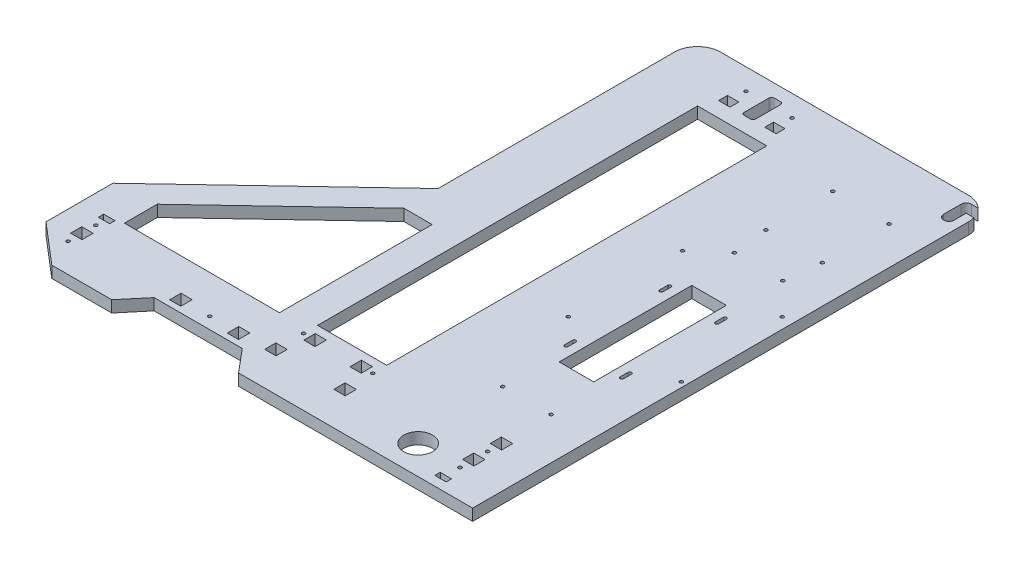
SolidWorks part; units mm, degrees
ref_plane "Front Plane" through (0, 0, 0) normal (0, 0, 1) x (1, 0, 0)
ref_plane "Top Plane" through (0, 0, 0) normal (0, 1, 0) x (1, 0, 0)
ref_plane "Right Plane" through (0, 0, 0) normal (1, 0, 0) x (0, 0, -1)
sketch "Sketch1" plane through (0, 0, 0) normal (0, 1, 0) x (1, 0, 0)
  line L0 (0, 0) -> (-235, 0)
  line L1 (-235, 0) -> (-235, -225)
  line L2 (-235, -225) -> (-380, -362)
  line L3 (-380, -362) -> (-380, -420)
  line L4 (-380, -420) -> (-345, -450)
  line L5 (-345, -450) -> (-293, -450)
  line L6 (-293, -450) -> (-263.6315, -415)
  line L7 (-263.6315, -415) -> (-212.3685, -415)
  line L8 (-212.3685, -415) -> (-183, -450)
  line L9 (-183, -450) -> (0, -450)
  line L10 (0, 0) -> (0, -450)
  line L12 (-293, -450) -> (-183, -450) construction
  dimension "D3" = 235
  dimension "D5" = 58
  dimension "D13" = 190
  dimension "D7" = 35
  dimension "D15" = 52
  dimension "D12" = 30
  dimension "D10" = 35
  dimension "D6" = 380
  dimension "D4" = 450
  dimension "D2" = 50
  dimension "D8" = 50
  dimension "D9" = 110
extrude "Boss-Extrude1" add sketch "Sketch1" along normal blind 10
sketch "Sketch16" plane through (0, 10, 0) normal (0, 1, 0) x (1, 0, 0)
  line L0 (0, -450) -> (20, -450)
  line L1 (20, -450) -> (20, 0)
  line L2 (20, 0) -> (0, 0)
  line L3 (0, 0) -> (0, -450)
  dimension "D1" = 20
  dimension "D2" = 90
extrude "Boss-Extrude2" add sketch "Sketch16" against normal through all
sketch "Sketch2" plane through (0, 10, 0) normal (0, 1, 0) x (1, 0, 0)
  line L0 (-235, -225) -> (-235, -415) construction
  line L1 (-263.6315, -415) -> (-212.3685, -415) construction
  line L2 (-345, -450) -> (-345, -328.931) construction
  line L3 (-235, -225) -> (-380, -362) construction
  line L4 (-345, -358.5097) -> (-235, -254.5787)
  line L5 (-235, -254.5787) -> (-210.5, -254.5787)
  line L6 (-210.5, -254.5787) -> (-210.5, -387)
  line L7 (-210.5, -387) -> (-345, -387)
  line L8 (-345, -387) -> (-345, -358.5097)
  line L9 (0, -450) -> (0, 0) construction
  line L10 (-184.5, -380) -> (-124.5, -380)
  line L11 (-184.5, -380) -> (-184.5, -50.425)
  line L12 (-184.5, -50.425) -> (-124.5, -50.425)
  line L13 (-124.5, -380) -> (-124.5, -50.425)
  line L14 (-124.5, -392.1) -> (-184.5, -392.1) construction
  line L15 (-16, -450) -> (-16, 0) construction
  line L16 (20, 0) -> (-235, 0) construction
  line L17 (-355.9, -440.6571) -> (-355.9, -339.2297) construction
  line L18 (-20.925, -441.85) -> (-11.075, -441.85)
  line L19 (-20.925, -441.85) -> (-20.925, -432.15)
  line L20 (-20.925, -432.15) -> (-11.075, -432.15)
  line L21 (-11.075, -441.85) -> (-11.075, -432.15)
  line L22 (-20.925, -441.85) -> (-11.075, -432.15) construction
  line L23 (-20.925, -432.15) -> (-11.075, -441.85) construction
  line L24 (-20.925, -417.85) -> (-11.075, -417.85)
  line L25 (-20.925, -417.85) -> (-20.925, -408.15)
  line L26 (-20.925, -408.15) -> (-11.075, -408.15)
  line L27 (-11.075, -417.85) -> (-11.075, -408.15)
  line L28 (-20.925, -417.85) -> (-11.075, -408.15) construction
  line L29 (-20.925, -408.15) -> (-11.075, -417.85) construction
  line L30 (-380, -420) -> (-345, -450) construction
  line L32 (-350.975, -408.15) -> (-360.825, -408.15)
  line L33 (-350.975, -408.15) -> (-350.975, -417.85)
  line L34 (-350.975, -417.85) -> (-360.825, -417.85)
  line L35 (-360.825, -408.15) -> (-360.825, -417.85)
  line L36 (-350.975, -408.15) -> (-360.825, -417.85) construction
  line L37 (-350.975, -417.85) -> (-360.825, -408.15) construction
  line L38 (-183, -450) -> (20, -450) construction
  line L39 (-183, -450) -> (20, -450) construction
  line L40 (-173.749, -32.425) -> (-113.749, -32.425) construction
  line L41 (-154.5, -50.425) -> (-154.5, -32.425) construction
  line L42 (-179.425, -27.575) -> (-169.575, -27.575)
  line L43 (-179.425, -27.575) -> (-179.425, -37.275)
  line L44 (-179.425, -37.275) -> (-169.575, -37.275)
  line L45 (-169.575, -27.575) -> (-169.575, -37.275)
  line L46 (-179.425, -27.575) -> (-169.575, -37.275) construction
  line L47 (-179.425, -37.275) -> (-169.575, -27.575) construction
  line L48 (-129.575, -37.275) -> (-139.425, -27.575) construction
  line L49 (-129.575, -27.575) -> (-139.425, -37.275) construction
  line L50 (-139.425, -27.575) -> (-139.425, -37.275)
  line L51 (-129.575, -37.275) -> (-139.425, -37.275)
  line L52 (-129.575, -27.575) -> (-129.575, -37.275)
  line L53 (-129.575, -27.575) -> (-139.425, -27.575)
  line L54 (-174.5, -32.425) -> (-174.5, -18.425) construction
  line L55 (-134.5, -32.425) -> (-134.5, -18.425) construction
  line L56 (-154.5, -380) -> (-154.5, -450) construction
  line L57 (-174.5, -392.1) -> (-134.5, -392.1) construction
  line L58 (-129.65, -397.025) -> (-139.35, -387.175) construction
  line L59 (-179.35, -387.175) -> (-169.65, -387.175)
  line L60 (-179.35, -387.175) -> (-179.35, -397.025)
  line L61 (-179.35, -397.025) -> (-169.65, -397.025)
  line L62 (-169.65, -387.175) -> (-169.65, -397.025)
  line L63 (-179.35, -387.175) -> (-169.65, -397.025) construction
  line L64 (-179.35, -397.025) -> (-169.65, -387.175) construction
  line L65 (-129.65, -387.175) -> (-139.35, -397.025) construction
  line L66 (-139.35, -387.175) -> (-139.35, -397.025)
  line L67 (-129.65, -397.025) -> (-139.35, -397.025)
  line L68 (-129.65, -387.175) -> (-129.65, -397.025)
  line L69 (-129.65, -387.175) -> (-139.35, -387.175)
  line L70 (-119.575, -420.95) -> (-129.425, -411.25) construction
  line L71 (-189.425, -411.25) -> (-179.575, -411.25)
  line L72 (-189.425, -411.25) -> (-189.425, -420.95)
  line L73 (-189.425, -420.95) -> (-179.575, -420.95)
  line L74 (-179.575, -411.25) -> (-179.575, -420.95)
  line L75 (-189.425, -411.25) -> (-179.575, -420.95) construction
  line L76 (-189.425, -420.95) -> (-179.575, -411.25) construction
  line L77 (-119.575, -411.25) -> (-129.425, -420.95) construction
  line L78 (-129.425, -411.25) -> (-129.425, -420.95)
  line L79 (-119.575, -420.95) -> (-129.425, -420.95)
  line L80 (-119.575, -411.25) -> (-119.575, -420.95)
  line L81 (-119.575, -411.25) -> (-129.425, -411.25)
  line L82 (-360.825, -408.15) -> (-11.075, -408.15) construction
  line L83 (-350.975, -393.85) -> (-360.825, -393.85)
  line L84 (-350.975, -393.85) -> (-350.975, -384.15)
  line L85 (-350.975, -384.15) -> (-360.825, -384.15)
  line L86 (-360.825, -393.85) -> (-360.825, -384.15)
  line L87 (-350.975, -393.85) -> (-360.825, -384.15) construction
  line L88 (-350.975, -384.15) -> (-360.825, -393.85) construction
  line L89 (-11.075, -384.15) -> (-20.925, -384.15)
  line L90 (-11.075, -384.15) -> (-11.075, -393.85)
  line L91 (-11.075, -393.85) -> (-20.925, -393.85)
  line L92 (-20.925, -384.15) -> (-20.925, -393.85)
  line L93 (-11.075, -384.15) -> (-20.925, -393.85) construction
  line L94 (-11.075, -393.85) -> (-20.925, -384.15) construction
  circle A0 centre (-16, -425) radius 1.45
  circle A1 centre (-16, -401) radius 1.45
  circle A2 centre (-355.9, -425) radius 1.45
  circle A3 centre (-355.9, -401) radius 1.45
  circle A4 centre (-174.5, -18.425) radius 1.45
  circle A5 centre (-134.5, -18.425) radius 1.45
  circle A6 centre (-124.5, -392.1) radius 1.45
  circle A7 centre (-184.5, -392.1) radius 1.45
  point P25 (-16, -437)
  point P30 (-16, -413)
  point P44 (-355.9, -413)
  point P58 (-355.9, -389)
  point P61 (-174.5, -32.425)
  point P72 (-134.5, -32.425)
  point P85 (-174.5, -392.1)
  point P94 (-134.5, -392.1)
  point P95 (-184.5, -416.1)
  point P104 (-124.5, -416.1)
  point P105 (-154.5, -392.1)
  point P111 (-16, -389)
  dimension "D13" = 2.9
  dimension "D14" = 2.9
  dimension "D23" = 2.9
  dimension "D24" = 2.9
  dimension "D31" = 2.9
  dimension "D37" = 2.9
  dimension "D1" = 21.5
  dimension "D2" = 28
  dimension "D3" = 24.5
  dimension "D4" = 60
  dimension "D7" = 26
  dimension "D8" = 9.7
  dimension "D9" = 9.85
  dimension "D10" = 9.85
  dimension "D11" = 9.7
  dimension "D12" = 24
  dimension "D15" = 24
  dimension "D19" = 9.85
  dimension "D20" = 9.7
  dimension "D26" = 12
  dimension "D27" = 9.85
  dimension "D28" = 9.7
  dimension "D33" = 9.7
  dimension "D38" = 9.85
  dimension "D39" = 9.7
  dimension "D41" = 24
  dimension "D34" = 30
  dimension "D36" = 12.1
  dimension "D30" = 18
  dimension "D29" = 40
  dimension "D17" = 13
  dimension "D32" = 14
  dimension "D35" = 20
  dimension "D16" = 12
  dimension "D21" = 90
  dimension "D25" = 24
  dimension "D5" = 359.75
  dimension "D22" = 349.75
  dimension "D40" = 30
  dimension "D6" = 70
  dimension "D42" = 0
  dimension "D43" = 0
  dimension "D18" = 16
  dimension "D44" = 9.85
  dimension "D45" = 24
  dimension "D46" = 24
extrude "Cut-Extrude1" cut sketch "Sketch2" against normal through all
fillet "Fillet1" radius 20 2 edges at (-235, 5, 0) (20, 5, 0)
sketch "Sketch11" plane through (0, 10, 0) normal (0, 1, 0) x (1, 0, 0)
  line L0 (-124.5, -215.2125) -> (20, -215.2125) construction
  line L1 (20, -450) -> (20, -20) construction
  line L3 (-52.25, -215.2125) -> (-52.25, -450) construction
  line L6 (-124.5, -380) -> (-124.5, -50.425) construction
  line L8 (-183, -450) -> (20, -450) construction
  circle A0 centre (-52.25, -425) radius 12.5
  circle A1 centre (-16, -425) radius 1.45 construction
  dimension "D1" = 25
  dimension "D2" = 0
  dimension "D3" = 0
extrude "WiringHole" cut sketch "Sketch11" against normal through all
sketch "Sketch9" [suppressed] plane through (0, 10, 0) normal (0, 1, 0) x (1, 0, 0)
  line L0 (-52.25, -412.5) -> (-52.25, 0) construction
  line L1 (0, 0) -> (-215, 0) construction
  line L2 (-124.5, -215.2125) -> (20, -215.2125) construction
  line L3 (-124.5, -380) -> (-124.5, -50.425) construction
  line L4 (-27.25, -140.2125) -> (-27.25, -290.2125) construction
  line L6 (-77.25, -140.2125) -> (-27.25, -140.2125) construction
  line L7 (-27.25, -290.2125) -> (-77.25, -290.2125) construction
  line L8 (-77.25, -290.2125) -> (-77.25, -140.2125) construction
  line L9 (20, -450) -> (20, -20) construction
  circle A0 centre (-52.25, -425) radius 12.5 construction
  circle A1 centre (-77.25, -140.2125) radius 1.95
  circle A2 centre (-27.25, -140.2125) radius 1.95
  circle A3 centre (-27.25, -290.2125) radius 1.95
  circle A4 centre (-77.25, -290.2125) radius 1.95
  dimension "D4" = 3.9
  dimension "D1" = 50
  dimension "D2" = 150
  dimension "D5" = 25
extrude "MountingHoles-PSU" [suppressed] cut sketch "Sketch9" against normal through all
sketch "Sketch25" [suppressed] plane through (0, 10, 0) normal (0, 1, 0) x (1, 0, 0)
  line L0 (-11.075, -417.85) -> (-11.075, -408.15) construction
  line L1 (-360.825, -408.15) -> (-350.975, -408.15)
  line L2 (-360.825, -408.15) -> (-360.825, -413.15)
  line L3 (-360.825, -413.15) -> (-350.975, -413.15)
  line L4 (-350.975, -408.15) -> (-350.975, -413.15)
  line L5 (-350.975, -417.85) -> (-350.975, -408.15) construction
  line L6 (-20.925, -408.15) -> (-11.075, -408.15)
  line L7 (-20.925, -408.15) -> (-20.925, -413.15)
  line L8 (-20.925, -413.15) -> (-11.075, -413.15)
  line L9 (-11.075, -408.15) -> (-11.075, -413.15)
  dimension "D1" = 5
  dimension "D2" = 5
extrude "SlotKeyingRight" [suppressed] add sketch "Sketch25" against normal through all
sketch "Sketch10" plane through (0, 10, 0) normal (0, 1, 0) x (1, 0, 0)
  line L0 (-124.5, -215.2125) -> (20, -215.2125) construction
  line L1 (20, -450) -> (20, -20) construction
  line L2 (-52.25, -245.2125) -> (-22.25, -245.2125) construction
  line L3 (-37.25, -210.225) -> (-37.25, 0) construction
  line L4 (-52.25, -215.2125) -> (-52.25, -184.5972) construction
  line L7 (-124.5, -380) -> (-124.5, -50.425) construction
  line L8 (-52.25, -302.7125) -> (-22.25, -302.7125)
  line L9 (-52.25, -302.7125) -> (-52.25, -187.7125)
  line L10 (-52.25, -187.7125) -> (-22.25, -187.7125)
  line L11 (-22.25, -302.7125) -> (-22.25, -187.7125)
  line L12 (-52.25, -302.7125) -> (-22.25, -187.7125) construction
  line L13 (-52.25, -187.7125) -> (-22.25, -302.7125) construction
  line L15 (0, 0) -> (-215, 0) construction
  line L17 (-37.25, -210.225) -> (-37.25, -450) construction
  line L18 (-183, -450) -> (20, -450) construction
  line L19 (-64.75, -215.2125) -> (-39.75, -215.2125) construction
  line L20 (-37.25, -302.7125) -> (-37.25, -187.7125) construction
  dimension "D1" = 30
  dimension "D2" = 115
  dimension "D3" = 0
  dimension "D4" = 0
  dimension "D5" = 0
  dimension "D6" = 30
  dimension "D7" = 15
extrude "WiringSlot" cut sketch "Sketch10" against normal through all
sketch "CenterLines" plane through (0, 10, 0) normal (0, 1, 0) x (1, 0, 0)
  line L0 (-37.25, -302.7125) -> (-37.25, -187.7125) construction
  line L1 (-52.25, -302.7125) -> (-22.25, -302.7125) construction
  line L2 (-22.25, -187.7125) -> (-52.25, -187.7125) construction
  line L3 (-52.25, -245.2125) -> (-22.25, -245.2125) construction
  line L4 (-52.25, -187.7125) -> (-52.25, -302.7125) construction
  line L5 (-22.25, -302.7125) -> (-22.25, -187.7125) construction
ref_plane "Plane1" through (-37.25, 0, 0) normal (1, 0, 0) x (0, 0, -1)
sketch "Sketch6" plane through (0, 10, 0) normal (0, 1, 0) x (1, 0, 0)
  line L0 (-37.25, -302.7125) -> (-37.25, -187.7125) construction
  line L1 (-61.35, -242.7125) -> (-13.15, -242.7125) construction
  line L2 (-13.15, -197.9625) -> (-13.15, -280.4625) construction
  line L3 (-52.25, -302.7125) -> (-22.25, -302.7125) construction
  line L4 (-52.25, -240.2125) -> (-22.25, -240.2125) construction
  line L5 (-22.25, -187.7125) -> (-52.25, -187.7125) construction
  line L6 (-13.15, -197.9625) -> (-13.15, -204.9625) construction
  line L7 (-11.7, -197.9625) -> (-11.7, -204.9625)
  line L8 (-14.6, -197.9625) -> (-14.6, -204.9625)
  line L9 (-52.25, -245.2125) -> (-22.25, -245.2125) construction
  line L10 (-52.25, -187.7125) -> (-52.25, -302.7125) construction
  line L11 (-22.25, -302.7125) -> (-22.25, -187.7125) construction
  line L12 (-13.15, -287.4625) -> (-13.15, -280.4625) construction
  line L13 (-14.6, -287.4625) -> (-14.6, -280.4625)
  line L14 (-61.35, -280.4625) -> (-61.35, -204.9625) construction
  line L15 (-13.15, -287.4625) -> (-13.15, -204.9625) construction
  line L16 (-11.7, -287.4625) -> (-11.7, -280.4625)
  arc A2 (-11.7, -197.9625) -> (-14.6, -197.9625) centre (-13.15, -197.9625) ccw
  arc A3 (-14.6, -204.9625) -> (-11.7, -204.9625) centre (-13.15, -204.9625) ccw
  circle A4 centre (-61.35, -280.4625) radius 1.45
  circle A6 centre (-61.35, -204.9625) radius 1.45
  arc A8 (-14.6, -287.4625) -> (-11.7, -287.4625) centre (-13.15, -287.4625) ccw
  arc A9 (-11.7, -280.4625) -> (-14.6, -280.4625) centre (-13.15, -280.4625) ccw
  point P20 (-13.15, -201.4625)
  point P25 (-13.15, -283.9625)
  dimension "D8" = 2.9
  dimension "D12" = 2.9
  dimension "D4" = 1.45
  dimension "D5" = 1.45
  dimension "D11" = 82.5
  dimension "D14" = 75.5
  dimension "D2" = 24.1
  dimension "D3" = 48.2
  dimension "D6" = 2.5
  dimension "D9" = 7
  dimension "D10" = 7
extrude "MountingHoles-RAMPS" cut sketch "Sketch6" against normal through all
mirror "Mirror1" about plane through (-37.25, 0, 0) normal (1, 0, 0) of "MountingHoles-RAMPS"
sketch "Sketch5" plane through (0, 10, 0) normal (0, 1, 0) x (1, 0, 0)
  line L0 (-22.25, -245.2125) -> (-52.25, -245.2125) construction
  line L3 (-22.25, -302.7125) -> (-22.25, -187.7125) construction
  line L5 (-52.25, -187.7125) -> (-52.25, -302.7125) construction
  line L7 (-16.25, -144.7125) -> (-58.25, -144.7125) construction
  line L8 (-16.25, -345.7125) -> (-58.25, -345.7125) construction
  line L9 (-37.25, -245.2125) -> (-37.25, -144.7125) construction
  line L10 (-37.25, -245.2125) -> (-37.25, -345.7125) construction
  circle A0 centre (-58.25, -144.7125) radius 1.45
  circle A1 centre (-16.25, -144.7125) radius 1.45
  circle A2 centre (-16.25, -345.7125) radius 1.45
  circle A3 centre (-58.25, -345.7125) radius 1.45
  point P17 (-37.25, -144.7125)
  point P22 (-37.25, -345.7125)
  dimension "D2" = 2.9
  dimension "D5" = 2.9
  dimension "D6" = 2.9
  dimension "D7" = 2.9
  dimension "D3" = 201
  dimension "D4" = 100.5
  dimension "D8" = 21
  dimension "D9" = 21
  dimension "D10" = 100.5
extrude "MountingHoles-Melzi" cut sketch "Sketch5" against normal through all
sketch "Sketch13" plane through (0, 0, 0) normal (0, -1, 0) x (-1, 0, 0)
  line L0 (52.25, -215.2125) -> (124.5, -215.2125) construction
  line L1 (124.5, -380) -> (124.5, -50.425) construction
  line L2 (82.25, -264.7275) -> (82.25, -165.6975) construction
  line L3 (37.25, -302.7125) -> (37.25, -187.7125) construction
  line L4 (52.25, -187.7125) -> (52.25, -302.7125) construction
  line L6 (82.25, -264.7275) -> (-15.65, -264.7275) construction
  circle A0 centre (82.25, -165.6975) radius 1.45
  circle A1 centre (82.25, -264.7275) radius 1.45
  circle A2 centre (-10.59, -172.1775) radius 1.45
  circle A3 centre (-15.65, -264.7275) radius 1.45
  point P11 (82.25, -215.2125)
  dimension "D8" = 2.9
  dimension "D6" = 2.9
  dimension "D1" = 2.9
  dimension "D2" = 49.515
  dimension "D3" = 45
  dimension "D4" = 6.48
  dimension "D5" = 92.84
  dimension "D7" = 97.9
extrude "Mountingholes-Smoothieboard" cut sketch "Sketch13" against normal through all
mirror "Flipped" [suppressed] about plane through (-37.25, 0, 0) normal (1, 0, 0)
sketch "Sketch21" plane through (0, 10, 0) normal (0, 1, 0) x (1, 0, 0)
  line L0 (-37.25, -187.7125) -> (-37.25, 0) construction
  line L1 (-22.25, -187.7125) -> (-52.25, -187.7125) construction
  line L2 (0, 0) -> (-215, 0) construction
  line L3 (-37.25, -85) -> (-23.3697, -85) construction
  circle A0 centre (-12.75, -56) radius 1.45
  circle A1 centre (-61.75, -56) radius 1.45
  circle A2 centre (-61.75, -114) radius 1.45
  circle A3 centre (-12.75, -114) radius 1.45
  dimension "D1" = 2.9
  dimension "D2" = 24.5
  dimension "D3" = 29
  dimension "D4" = 85
extrude "Pi" cut sketch "Sketch21" against normal through all
sketch "Sketch24" plane through (0, 10, 0) normal (0, 1, 0) x (1, 0, 0)
  line L0 (-350.975, -393.85) -> (-350.975, -384.15) construction
  line L1 (-11.075, -441.85) -> (-11.075, -432.15) construction
  line L2 (-20.925, -432.15) -> (-11.075, -432.15)
  line L3 (-360.825, -384.15) -> (-350.975, -384.15)
  line L4 (-360.825, -384.15) -> (-360.825, -389.15)
  line L5 (-360.825, -389.15) -> (-350.975, -389.15)
  line L6 (-350.975, -384.15) -> (-350.975, -389.15)
  line L7 (-20.925, -432.15) -> (-20.925, -437.15)
  line L8 (-20.925, -437.15) -> (-11.075, -437.15)
  line L9 (-11.075, -432.15) -> (-11.075, -437.15)
  line L10 (-169.575, -37.275) -> (-169.575, -27.575) construction
  line L11 (-179.425, -27.575) -> (-169.575, -27.575)
  line L12 (-179.425, -27.575) -> (-179.425, -29.575)
  line L13 (-179.425, -29.575) -> (-169.575, -29.575)
  line L14 (-169.575, -27.575) -> (-169.575, -29.575)
  line L15 (-129.575, -37.275) -> (-129.575, -27.575) construction
  line L16 (-139.425, -27.575) -> (-129.575, -27.575)
  line L17 (-139.425, -27.575) -> (-139.425, -29.575)
  line L18 (-139.425, -29.575) -> (-129.575, -29.575)
  line L19 (-129.575, -27.575) -> (-129.575, -29.575)
  line L20 (-169.575, -29.575) -> (-139.425, -29.575) construction
  dimension "D1" = 5
  dimension "D2" = 5
  dimension "D3" = 2
extrude "SlotKeyingLeft" add sketch "Sketch24" against normal through all
sketch "Sketch26" plane through (0, 10, 0) normal (0, 1, 0) x (1, 0, 0)
  line L0 (-169.575, -33.425) -> (-139.425, -33.425) construction
  line L1 (-169.575, -37.275) -> (-169.575, -29.575) construction
  line L2 (-139.425, -29.575) -> (-139.425, -37.275) construction
  line L3 (-154.5, -33.425) -> (-154.5, -24.275) construction
  line L4 (-154.5, -37.275) -> (-169.575, -37.275) construction
  line L5 (-157.5, -11.275) -> (-151.5, -11.275)
  line L6 (-159.5, -13.275) -> (-159.5, -35.275)
  line L7 (-157.5, -37.275) -> (-151.5, -37.275)
  line L8 (-149.5, -13.275) -> (-149.5, -35.275)
  line L9 (-159.5, -11.275) -> (-149.5, -37.275) construction
  line L10 (-159.5, -37.275) -> (-149.5, -11.275) construction
  arc A0 (-159.5, -35.275) -> (-157.5, -37.275) centre (-157.5, -35.275) ccw
  arc A1 (-151.5, -37.275) -> (-149.5, -35.275) centre (-151.5, -35.275) ccw
  arc A2 (-151.5, -11.275) -> (-149.5, -13.275) centre (-151.5, -13.275) cw
  arc A3 (-157.5, -11.275) -> (-159.5, -13.275) centre (-157.5, -13.275) ccw
  dimension "D4" = 2
  dimension "D1" = 10
  dimension "D2" = 26
extrude "TopWiringSlot" cut sketch "Sketch26" against normal through all
sketch "Sketch17" plane through (0, 10, 0) normal (0, 1, 0) x (1, 0, 0)
  line L0 (0, 0) -> (20, 0) construction
  line L1 (20, -23.6361) -> (20, 0) construction
  line L2 (20, -450) -> (20, -20) construction
  line L3 (20, -10) -> (8, -10) construction
  line L4 (20, -14.5) -> (8, -14.5)
  line L5 (20, -5.5) -> (8, -5.5)
  arc A0 (20, -14.5) -> (20, -5.5) centre (20, -10) ccw
  arc A1 (8, -5.5) -> (8, -14.5) centre (8, -10) ccw
  point P8 (14, -10)
  dimension "D1" = 9
  dimension "D2" = 12
  dimension "D3" = 10
extrude "Cut-Extrude3" cut sketch "Sketch17" against normal through all
sketch "Sketch18" plane through (0, 10, 0) normal (0, 1, 0) x (1, 0, 0)
  line L0 (8, -5.5) -> (8, -14.5) construction
  line L1 (3.5, -10) -> (8, -10) construction
  line L2 (8, -10) -> (8, -25) construction
  line L3 (12.5, -10) -> (12.5, -25)
  line L4 (3.5, -10) -> (3.5, -25)
  arc A0 (8, -5.5) -> (8, -14.5) centre (8, -10) ccw construction
  arc A1 (12.5, -10) -> (3.5, -10) centre (8, -10) ccw
  arc A2 (3.5, -25) -> (12.5, -25) centre (8, -25) ccw
  point P10 (8, -17.5)
  dimension "D1" = 9
  dimension "D2" = 0
  dimension "D3" = 15
extrude "Cut-Extrude4" cut sketch "Sketch18" against normal through all
sketch "Sketch19" plane through (0, 10, 0) normal (0, 1, 0) x (1, 0, 0)
  line L0 (-2, -25) -> (18, -25) construction
  line L1 (8, -25) -> (8, -5.5) construction
  circle A0 centre (18, -25) radius 1.45
  arc A1 (8, -5.5) -> (3.5, -10) centre (8, -10) ccw construction
  circle A2 centre (-2, -25) radius 1.45
  dimension "D2" = 2.9
extrude "Cut-Extrude5" [suppressed] cut sketch "Sketch19" against normal through all
sketch "Sketch22" plane through (0, 10, 0) normal (0, 1, 0) x (1, 0, 0)
  line L0 (-276.218, -430) -> (-199.782, -430)
  line L1 (-293, -450) -> (-263.6315, -415) construction
  line L2 (-212.3685, -415) -> (-183, -450) construction
  line L3 (-199.782, -430) -> (-212.3685, -415)
  line L4 (-212.3685, -415) -> (-263.6315, -415)
  line L5 (-263.6315, -415) -> (-276.218, -430)
  dimension "D1" = 15
extrude "Boss-Extrude3" add sketch "Sketch22" against normal through all
sketch "Sketch23" plane through (0, 10, 0) normal (0, 1, 0) x (1, 0, 0)
  line L0 (-238, -430) -> (-238, -387) construction
  line L1 (-276.218, -430) -> (-199.782, -430) construction
  line L2 (-345, -387) -> (-210.5, -387) construction
  line L3 (-213, -420) -> (-263, -420) construction
  line L4 (-179.35, -387.175) -> (-179.35, -397.025) construction
  line L5 (-267.85, -415.075) -> (-258.15, -415.075)
  line L6 (-267.85, -415.075) -> (-267.85, -424.925)
  line L7 (-267.85, -424.925) -> (-258.15, -424.925)
  line L8 (-258.15, -415.075) -> (-258.15, -424.925)
  line L9 (-267.85, -415.075) -> (-258.15, -424.925) construction
  line L10 (-267.85, -424.925) -> (-258.15, -415.075) construction
  line L11 (-208.15, -424.925) -> (-217.85, -415.075) construction
  line L12 (-208.15, -415.075) -> (-217.85, -424.925) construction
  line L13 (-217.85, -415.075) -> (-217.85, -424.925)
  line L14 (-208.15, -424.925) -> (-217.85, -424.925)
  line L15 (-208.15, -415.075) -> (-208.15, -424.925)
  line L16 (-208.15, -415.075) -> (-217.85, -415.075)
  circle A0 centre (-238, -420) radius 1.45
  point P19 (-238, -420)
  dimension "D4" = 2.9
  dimension "D1" = 9.7
  dimension "D3" = 10
extrude "Cut-Extrude6" cut sketch "Sketch23" against normal through all
equation "\"Y-ROD-SPACING\"=75"
equation "\"Y-BED-OFFSET\"=2"
equation "\"Y-BED-ROD-INSET\"=3.5"
equation "\"T-SLOT-NUT-FILLET-RADIUS\"=0.5"
equation "\"T-SLOT-SCREW-SHAFT-RADIUS\"=1.55"
equation "\"T-SLOT-SCREW-SHAFT-CUTOUT-LENGTH\"=11"
equation "\"T-SLOT-NUT-DEPTH\"=3.5"
equation "\"T-SLOT-NUT-WIDTH\"=2.85"
equation "\"T-SLOT-NUT-END-DISTANCE\"=8"
equation "\"ACRYLIC-TAB-CUTOUT-SIZE\"=\"ACRYLIC-THICKNESS\"+\"ACRYLIC-TAB-TOLERANCE\"*2"
equation "\"ACRYLIC-TAB-WIDTH\"=\"ACRYLIC-THICKNESS\""
equation "\"ACRYLIC-M3-HOLE\"=2.9"
equation "\"SMOOTHROD-CAP-SCREW-DISTANCE\"=20"
equation "\"FRAME-WIDTH-INNER\"=370"
equation "\"D24@Sketch2\"=\"ACRYLIC-M3-HOLE\""
equation "\"D23@Sketch2\"=\"ACRYLIC-M3-HOLE\""
equation "\"D19@Sketch2\"=\"ACRYLIC-THICKNESS\"-\"KERF\"*2"
equation "\"D20@Sketch2\"=\"ACRYLIC-TAB-WIDTH\"-\"KERF\"*4"
equation "\"D37@Sketch2\"=\"ACRYLIC-M3-HOLE\""
equation "\"D33@Sketch2\"=\"ACRYLIC-TAB-WIDTH\"-\"KERF\"*4"
equation "\"D38@Sketch2\"=\"ACRYLIC-THICKNESS\"-\"KERF\"*2"
equation "\"D39@Sketch2\"=\"ACRYLIC-TAB-WIDTH\"-\"KERF\"*4"
equation "\"D13@Sketch2\"=\"ACRYLIC-M3-HOLE\""
equation "\"D14@Sketch2\"=\"ACRYLIC-M3-HOLE\""
equation "\"D8@Sketch2\"=\"ACRYLIC-TAB-WIDTH\"-\"KERF\"*4"
equation "\"D9@Sketch2\"=\"ACRYLIC-THICKNESS\"-\"KERF\"*2"
equation "\"D10@Sketch2\"=\"ACRYLIC-THICKNESS\"-\"KERF\"*2"
equation "\"D11@Sketch2\"=\"ACRYLIC-TAB-WIDTH\"-\"KERF\"*4"
equation "\"D31@Sketch2\"=\"ACRYLIC-M3-HOLE\""
equation "\"D27@Sketch2\"=\"ACRYLIC-THICKNESS\"-\"KERF\"*2"
equation "\"D28@Sketch2\"=\"ACRYLIC-TAB-WIDTH\"-\"KERF\"*4"
equation "\"NEMA17-HOLE-SPACING\"=31"
equation "\"NEMA17-CENTRAL-CUTOUT\"=22.5"
equation "\"Z-BRACKET-REACH\"=57"
equation "\"TOP-BRACKET-SPACING\"=40"
equation "\"D29@Sketch2\"=\"TOP-BRACKET-SPACING\""
equation "\"ACRYLIC-THICKNESS\"=10"
equation "\"SMOOTHROD-Z-LENGTH\"=350"
equation "\"D5@Sketch2\"=\"SMOOTHROD-Z-LENGTH\"-\"SMOOTHROD-TIGHTENING-HEADROOM\"+10"
equation "\"SMOOTHROD-X-LENGTH\"=350"
equation "\"SMOOTHROD-Y-LENGTH\"=350"
equation "\"D22@Sketch2\"=\"SMOOTHROD-Y-LENGTH\"-\"SMOOTHROD-TIGHTENING-HEADROOM\""
equation "\"SMOOTHROD-TIGHTENING-HEADROOM\"=.25"
equation "\"X-ROD-SPACING\"=45"
equation "\"Z-ROD-SPACING\"=17.5"
equation "\"LEADSCREW-Z-LENGTH\"=300"
equation "\"SCREW-HEAD-RADIUS\"=6"
equation "\"PRINTED-X-SMOOTHROD-DIAMETER\"=8.8"
equation "\"PRINTED-X-SMOOTHROD-CUTOUT\"=10"
equation "\"PRINTED-X-BASE-HEIGHT\"=10"
equation "\"PRINTED-LM8UU-CUTOUT-SIZE\"=15.5"
equation "\"PRINTED-LM8UU-CUTOUT-LENGTH\"=24.5"
equation "\"PRINTED-X-IDLER-HEIGHT\"=16"
equation "\"PSU-MOUNTING-WIDTH\"=50"
equation "\"PSU-MOUNTING-HEIGHT\"=150"
equation "\"D1@Sketch9\"=\"PSU-MOUNTING-WIDTH\""
equation "\"D1@Boss-Extrude1\"=\"ACRYLIC-THICKNESS\""
equation "\"D6@Sketch1\"=\"SMOOTHROD-Y-LENGTH\"+30"
equation "\"D4@Sketch9\"=\"ACRYLIC-M4-HOLE\""
equation "\"D2@Sketch9\"=\"PSU-MOUNTING-HEIGHT\""
equation "\"D5@Sketch9\"=\"PSU-MOUNTING-WIDTH\"/2"
equation "\"D4@Sketch1\"=\"SMOOTHROD-Z-LENGTH\"+100"
equation "\"D8@Sketch6\"=\"ACRYLIC-M3-HOLE\""
equation "\"D12@Sketch6\"=\"ACRYLIC-M3-HOLE\""
equation "\"D2@Sketch5\"=\"ACRYLIC-M3-HOLE\""
equation "\"D5@Sketch5\"=\"ACRYLIC-M3-HOLE\""
equation "\"D6@Sketch5\"=\"ACRYLIC-M3-HOLE\""
equation "\"D7@Sketch5\"=\"ACRYLIC-M3-HOLE\""
equation "\"D1@Sketch13\"=\"ACRYLIC-M3-HOLE\""
equation "\"D6@Sketch13\"=\"ACRYLIC-M3-HOLE\""
equation "\"D8@Sketch13\"=\"ACRYLIC-M3-HOLE\""
equation "\"D4@Sketch6\"=\"ACRYLIC-M3-HOLE\"/2"
equation "\"D5@Sketch6\"=\"ACRYLIC-M3-HOLE\"/2"
equation "\"Y-BED-SCREW-SPACING\"=209"
equation "\"Y-BED-SCREW-CUTOUT-SLOT-HEIGHT\"=2.5"
equation "\"ACRYLIC-THICKNESS2\"=4.5"
equation "\"ACRYLIC-TAB-TOLERANCE\"=-.05"
equation "\"Z-ROD-INSET\"=13.5"
equation "\"SCREW-LENGTH-FRAME\"=\"ACRYLIC-THICKNESS\" + 10"
equation "\"SCREW-LENGTH-MOTOR\"=\"ACRYLIC-THICKNESS\" + 5"
equation "\"SCREW-LENGTH-EXTRUDER\"=28"
equation "\"Y-BELT-TO-ROD-DISTANCE\"=20"
equation "\"SPOOL-HOLDER-ROD-SPACING\"=150"
equation "\"ACRYLIC-X-CARRIAGE-WIDTH\"=55"
equation "\"ACRYLIC-X-CARRIAGE-HEIGHT\"=75"
equation "\"ACRYLIC-X-CARRIAGE-LM8UU-CUTOUT-WIDTH\"=24.25"
equation "\"ACRYLIC-X-CARRIAGE-SCREW-SPACING-X\"=15"
equation "\"ACRYLIC-X-CARRIAGE-SCREW-SPACING-Y\"=33"
equation "\"ACRYLIC-X-CARRIAGE-CENTER-TAB-SPACING\"=14"
equation "\"ACRYLIC-X-CARRIAGE-EXTRUDER-OFFSET\"=26"
equation "\"ACRYLIC-X-CARRIAGE-EXTRUDER-ANGLE\"=90"
equation "\"ACRYLIC-X-CARRIAGE-EXTRUDER-SHELF-DEPTH\"=\"ACRYLIC-X-CARRIAGE-EXTRUDER-OFFSET\" + 28"
equation "\"ACRYLIC-X-CARRIAGE-EXTRUDER-BRACE-SPACING\"=23"
equation "\"ACRYLIC-X-CARRIAGE-EXTRUDER-BRACE-TAB-OFFSET\"=20"
equation "\"ACRYLIC-X-CARRIAGE-EXTRUDER-BRACE-HEIGHT\"=35"
equation "\"ACRYLIC-X-CARRIAGE-EXTRUDER-BRACE-SCREW-SPACING\"=22"
equation "\"D1@Sketch19\"=\"SMOOTHROD-CAP-SCREW-DISTANCE\"/2"
equation "\"D2@Sketch19\"=\"ACRYLIC-M3-HOLE\""
equation "\"D1@Sketch21\"=\"ACRYLIC-M3-HOLE\""
equation "\"KERF\"=0.075"
equation "\"PRINTED-M3-HOLE\"=3.5"
equation "\"PRINTED-M3-NUT-AF\"=6.25"
equation "\"ACRYLIC-X-CARRIAGE-LM8UU-CUTOUT-HEIGHT\"=11.0"
equation "\"ACRYLIC-X-CARRIAGE-DUAL-WIDTH-MULTIPLIER\"=1.65"
equation "\"ACRYLIC-X-CARRIAGE-DUAL-HOTEND-SPACING\"=42"
equation "\"ACRYLIC-X-CARRIAGE-DUAL-WIDTH\"=75"
equation "\"ACRYLIC-X-CARRIAGE-DUAL-FAN-OFFSET\"=52"
equation "\"ACRYLIC-X-CARRIAGE-DUAL-FAN-HEIGHT\"=20"
equation "\"ACRYLIC-X-CARRIAGE-DUAL-HOTEND-SEPARATION\"=36"
equation "\"ACRYLIC-X-CARRIAGE-DUAL-MOUNT-PLATE-DEPTH\"=75"
equation "\"ACRYLIC-X-CARRIAGE-DUAL-MOUNT-BRACE-WIDTH\"=33"
equation "\"ACRYLIC-X-CARRIAGE-DUAL-MOUNT-SCREW-WIDTH\"=40"
equation "\"BLOWER-FAN-WIDTH\"=15"
equation "\"D44@Sketch2\"=\"ACRYLIC-THICKNESS\"-\"KERF\"*2"
equation "\"D1@Sketch23\"=10-\"KERF\"*4"
equation "\"D4@Sketch23\"=\"ACRYLIC-M3-HOLE\""
equation "\"ACRYLIC-THICKNESS-TAB-CUTOUT-WIDTH\"=\"ACRYLIC-THICKNESS\"-\"KERF\"*2"
equation "\"ACRYLIC-THICKNESS-TAB-CUTOUT-HEIGHT\"=\"ACRYLIC-TAB-WIDTH\"-\"KERF\"*4"
equation "\"ACRYLIC-THICKNESS2-TAB-CUTOUT-WIDTH\"=\"ACRYLIC-THICKNESS2\"-\"KERF\"*2"
equation "\"ACRYLIC-THICKNESS2-TAB-CUTOUT-HEIGHT\"=\"ACRYLIC-TAB-WIDTH\"-\"KERF\"*4"
equation "\"ACRYLIC-M4-HOLE\"=3.9"
